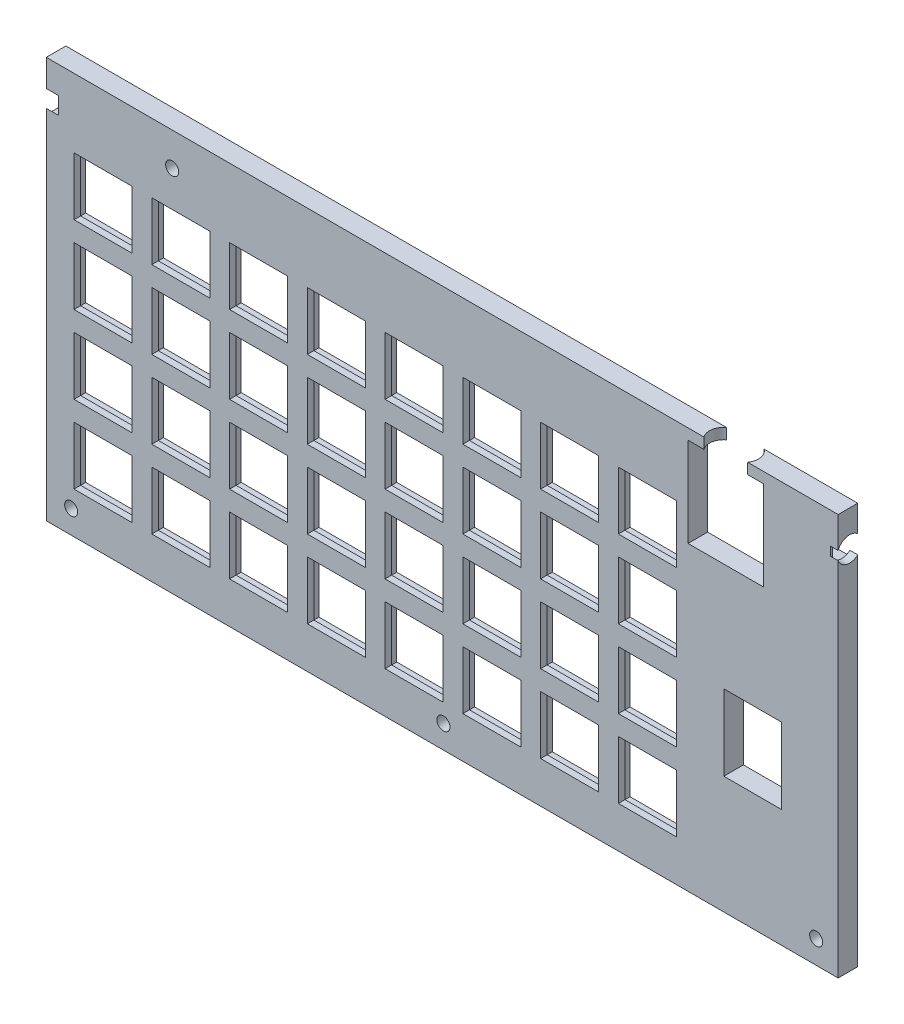
SolidWorks part; units mm, degrees
note: The reader was unsure of these and kept them because the rebuilt part matched: shared geometry of "Sketch1<5>", "Sketch1<6>", "Sketch1<7>", "Sketch4<3>", "Sketch5<3>".
other "Markup1"
sketch "Sketch7" plane through (238.5833, -190.4008, 4.8) normal (0.0408, -0.0399, 0.9984) x (0.9992, -0.0006, -0.0409)
material "Custom Plastic"
ref_plane "Front Plane" through (0, 0, 0) normal (0, 0, 1) x (1, 0, 0)
ref_plane "Top Plane" through (0, 0, 0) normal (0, 1, 0) x (1, 0, 0)
ref_plane "Right Plane" through (0, 0, 0) normal (1, 0, 0) x (0, 0, -1)
sketch "Sketch1" plane through (0, 0, 0) normal (0, 0, 1) x (1, 0, 0)
  line L0 (54.0943, -97.1368) -> (55.0943, -97.1368) construction
  line L1 (51.4043, -123.1268) -> (65.6043, -123.1268)
  line L2 (51.4043, -123.1268) -> (51.4043, -108.9268)
  line L3 (51.4043, -108.9268) -> (65.6043, -108.9268)
  line L4 (65.6043, -123.1268) -> (65.6043, -108.9268)
  line L5 (51.4043, -123.1268) -> (65.6043, -108.9268) construction
  line L6 (51.4043, -108.9268) -> (65.6043, -123.1268) construction
  line L7 (70.4543, -123.1268) -> (70.4543, -108.9268)
  line L8 (70.4543, -123.1268) -> (84.6543, -123.1268)
  line L9 (84.6543, -123.1268) -> (84.6543, -108.9268)
  line L10 (70.4543, -108.9268) -> (84.6543, -108.9268)
  line L11 (89.5043, -123.1268) -> (89.5043, -108.9268)
  line L12 (89.5043, -123.1268) -> (103.7043, -123.1268)
  line L13 (103.7043, -123.1268) -> (103.7043, -108.9268)
  line L14 (89.5043, -108.9268) -> (103.7043, -108.9268)
  line L15 (108.5543, -123.1268) -> (108.5543, -108.9268)
  line L16 (108.5543, -123.1268) -> (122.7543, -123.1268)
  line L17 (122.7543, -123.1268) -> (122.7543, -108.9268)
  line L18 (108.5543, -108.9268) -> (122.7543, -108.9268)
  line L19 (127.6043, -123.1268) -> (127.6043, -108.9268)
  line L20 (127.6043, -123.1268) -> (141.8043, -123.1268)
  line L21 (141.8043, -123.1268) -> (141.8043, -108.9268)
  line L22 (127.6043, -108.9268) -> (141.8043, -108.9268)
  line L23 (146.6543, -123.1268) -> (146.6543, -108.9268)
  line L24 (146.6543, -123.1268) -> (160.8543, -123.1268)
  line L25 (160.8543, -123.1268) -> (160.8543, -108.9268)
  line L26 (146.6543, -108.9268) -> (160.8543, -108.9268)
  line L27 (165.7043, -123.1268) -> (165.7043, -108.9268)
  line L28 (165.7043, -123.1268) -> (179.9043, -123.1268)
  line L29 (179.9043, -123.1268) -> (179.9043, -108.9268)
  line L30 (165.7043, -108.9268) -> (179.9043, -108.9268)
  line L31 (184.7543, -123.1268) -> (184.7543, -108.9268)
  line L32 (184.7543, -123.1268) -> (198.9543, -123.1268)
  line L33 (198.9543, -123.1268) -> (198.9543, -108.9268)
  line L34 (184.7543, -108.9268) -> (198.9543, -108.9268)
  line L35 (70.4543, -142.1768) -> (70.4543, -127.9768)
  line L36 (70.4543, -142.1768) -> (84.6543, -142.1768)
  line L37 (84.6543, -142.1768) -> (84.6543, -127.9768)
  line L38 (70.4543, -127.9768) -> (84.6543, -127.9768)
  line L39 (89.5043, -142.1768) -> (89.5043, -127.9768)
  line L40 (89.5043, -142.1768) -> (103.7043, -142.1768)
  line L41 (103.7043, -142.1768) -> (103.7043, -127.9768)
  line L42 (89.5043, -127.9768) -> (103.7043, -127.9768)
  line L43 (108.5543, -142.1768) -> (108.5543, -127.9768)
  line L44 (108.5543, -142.1768) -> (122.7543, -142.1768)
  line L45 (122.7543, -142.1768) -> (122.7543, -127.9768)
  line L46 (108.5543, -127.9768) -> (122.7543, -127.9768)
  line L47 (127.6043, -142.1768) -> (127.6043, -127.9768)
  line L48 (127.6043, -142.1768) -> (141.8043, -142.1768)
  line L49 (141.8043, -142.1768) -> (141.8043, -127.9768)
  line L50 (127.6043, -127.9768) -> (141.8043, -127.9768)
  line L51 (146.6543, -142.1768) -> (146.6543, -127.9768)
  line L52 (146.6543, -142.1768) -> (160.8543, -142.1768)
  line L53 (160.8543, -142.1768) -> (160.8543, -127.9768)
  line L54 (146.6543, -127.9768) -> (160.8543, -127.9768)
  line L55 (165.7043, -142.1768) -> (165.7043, -127.9768)
  line L56 (165.7043, -142.1768) -> (179.9043, -142.1768)
  line L57 (179.9043, -142.1768) -> (179.9043, -127.9768)
  line L58 (165.7043, -127.9768) -> (179.9043, -127.9768)
  line L59 (184.7543, -142.1768) -> (184.7543, -127.9768)
  line L60 (184.7543, -142.1768) -> (198.9543, -142.1768)
  line L61 (198.9543, -142.1768) -> (198.9543, -127.9768)
  line L62 (184.7543, -127.9768) -> (198.9543, -127.9768)
  line L63 (70.4543, -161.2268) -> (70.4543, -147.0268)
  line L64 (70.4543, -161.2268) -> (84.6543, -161.2268)
  line L65 (84.6543, -161.2268) -> (84.6543, -147.0268)
  line L66 (70.4543, -147.0268) -> (84.6543, -147.0268)
  line L67 (89.5043, -161.2268) -> (89.5043, -147.0268)
  line L68 (89.5043, -161.2268) -> (103.7043, -161.2268)
  line L69 (103.7043, -161.2268) -> (103.7043, -147.0268)
  line L70 (89.5043, -147.0268) -> (103.7043, -147.0268)
  line L71 (108.5543, -161.2268) -> (108.5543, -147.0268)
  line L72 (108.5543, -161.2268) -> (122.7543, -161.2268)
  line L73 (122.7543, -161.2268) -> (122.7543, -147.0268)
  line L74 (108.5543, -147.0268) -> (122.7543, -147.0268)
  line L75 (127.6043, -161.2268) -> (127.6043, -147.0268)
  line L76 (127.6043, -161.2268) -> (141.8043, -161.2268)
  line L77 (141.8043, -161.2268) -> (141.8043, -147.0268)
  line L78 (127.6043, -147.0268) -> (141.8043, -147.0268)
  line L79 (146.6543, -161.2268) -> (146.6543, -147.0268)
  line L80 (146.6543, -161.2268) -> (160.8543, -161.2268)
  line L81 (160.8543, -161.2268) -> (160.8543, -147.0268)
  line L82 (146.6543, -147.0268) -> (160.8543, -147.0268)
  line L83 (165.7043, -161.2268) -> (165.7043, -147.0268)
  line L84 (165.7043, -161.2268) -> (179.9043, -161.2268)
  line L85 (179.9043, -161.2268) -> (179.9043, -147.0268)
  line L86 (165.7043, -147.0268) -> (179.9043, -147.0268)
  line L87 (184.7543, -161.2268) -> (184.7543, -147.0268)
  line L88 (184.7543, -161.2268) -> (198.9543, -161.2268)
  line L89 (198.9543, -161.2268) -> (198.9543, -147.0268)
  line L90 (184.7543, -147.0268) -> (198.9543, -147.0268)
  line L91 (70.4543, -180.2768) -> (70.4543, -166.0768)
  line L92 (70.4543, -180.2768) -> (84.6543, -180.2768)
  line L93 (84.6543, -180.2768) -> (84.6543, -166.0768)
  line L94 (70.4543, -166.0768) -> (84.6543, -166.0768)
  line L95 (89.5043, -180.2768) -> (89.5043, -166.0768)
  line L96 (89.5043, -180.2768) -> (103.7043, -180.2768)
  line L97 (103.7043, -180.2768) -> (103.7043, -166.0768)
  line L98 (89.5043, -166.0768) -> (103.7043, -166.0768)
  line L99 (108.5543, -180.2768) -> (108.5543, -166.0768)
  line L100 (108.5543, -180.2768) -> (122.7543, -180.2768)
  line L101 (122.7543, -180.2768) -> (122.7543, -166.0768)
  line L102 (108.5543, -166.0768) -> (122.7543, -166.0768)
  line L103 (127.6043, -180.2768) -> (127.6043, -166.0768)
  line L104 (127.6043, -180.2768) -> (141.8043, -180.2768)
  line L105 (141.8043, -180.2768) -> (141.8043, -166.0768)
  line L106 (127.6043, -166.0768) -> (141.8043, -166.0768)
  line L107 (146.6543, -180.2768) -> (146.6543, -166.0768)
  line L108 (146.6543, -180.2768) -> (160.8543, -180.2768)
  line L109 (160.8543, -180.2768) -> (160.8543, -166.0768)
  line L110 (146.6543, -166.0768) -> (160.8543, -166.0768)
  line L111 (165.7043, -180.2768) -> (165.7043, -166.0768)
  line L112 (165.7043, -180.2768) -> (179.9043, -180.2768)
  line L113 (179.9043, -180.2768) -> (179.9043, -166.0768)
  line L114 (165.7043, -166.0768) -> (179.9043, -166.0768)
  line L115 (184.7543, -180.2768) -> (184.7543, -166.0768)
  line L116 (184.7543, -180.2768) -> (198.9543, -180.2768)
  line L117 (198.9543, -180.2768) -> (198.9543, -166.0768)
  line L118 (184.7543, -166.0768) -> (198.9543, -166.0768)
  line L119 (51.4043, -142.1768) -> (51.4043, -127.9768)
  line L120 (51.4043, -142.1768) -> (65.6043, -142.1768)
  line L121 (65.6043, -142.1768) -> (65.6043, -127.9768)
  line L122 (51.4043, -127.9768) -> (65.6043, -127.9768)
  line L123 (51.4043, -161.2268) -> (51.4043, -147.0268)
  line L124 (51.4043, -161.2268) -> (65.6043, -161.2268)
  line L125 (65.6043, -161.2268) -> (65.6043, -147.0268)
  line L126 (51.4043, -147.0268) -> (65.6043, -147.0268)
  line L127 (51.4043, -180.2768) -> (51.4043, -166.0768)
  line L128 (51.4043, -180.2768) -> (65.6043, -180.2768)
  line L129 (65.6043, -180.2768) -> (65.6043, -166.0768)
  line L130 (51.4043, -166.0768) -> (65.6043, -166.0768)
  line L131 (238.5833, -190.4008) -> (238.5833, -173.7718) construction
  line L132 (44.6073, -92.0718) -> (238.5833, -92.0718)
  line L133 (44.6073, -92.0718) -> (44.6073, -190.4008)
  line L134 (44.6073, -190.4008) -> (238.5833, -190.4008)
  line L135 (238.5833, -92.0718) -> (238.5833, -190.4008)
  line L136 (44.6073, -190.4008) -> (44.6073, -103.6591) construction
  line L137 (238.5833, -190.4008) -> (44.6073, -190.4008) construction
  line L138 (149.2419, -92.0718) -> (44.6073, -92.0718) construction
  line L140 (130.7973, -100.9138) -> (130.7973, -98.8818) construction
  line L141 (53.3943, -97.3368) -> (53.3943, -96.9368)
  line L142 (53.3943, -96.9368) -> (55.7943, -96.9368)
  line L143 (55.7943, -96.9368) -> (55.7943, -97.3368)
  line L144 (55.7943, -97.3368) -> (59.7643, -97.3368)
  line L145 (59.7643, -97.3368) -> (59.7643, -104.2368)
  line L146 (59.7643, -104.2368) -> (56.7943, -104.2368)
  line L147 (56.7943, -104.2368) -> (56.7943, -104.6368)
  line L148 (56.7943, -104.6368) -> (54.3943, -104.6368)
  line L149 (54.3943, -104.6368) -> (54.3943, -104.2368)
  line L150 (54.3943, -104.2368) -> (44.6073, -104.2368)
  line L151 (44.6073, -104.2368) -> (44.6073, -97.3368)
  line L152 (44.6073, -97.3368) -> (53.3943, -97.3368)
  line L153 (49.9143, -97.5368) -> (50.7143, -97.5368) construction
  line L154 (56.4643, -97.5368) -> (57.2643, -97.5368) construction
  line L155 (50.7043, -104.0368) -> (49.9043, -104.0368) construction
  line L156 (56.0943, -104.4368) -> (55.0943, -104.4368) construction
  line L157 (58.4643, -104.0368) -> (57.6643, -104.0368) construction
  line L158 (59.5643, -103.9368) -> (59.5643, -97.6368) construction
  line L159 (238.5833, -104.2368) -> (230.8283, -104.2368)
  line L160 (230.8283, -104.2368) -> (230.8283, -104.6368)
  line L161 (230.8283, -104.6368) -> (228.4283, -104.6368)
  line L162 (228.4283, -104.6368) -> (228.4283, -104.2368)
  line L163 (228.4283, -104.2368) -> (224.4583, -104.2368)
  line L164 (224.4583, -104.2368) -> (224.4583, -97.3368)
  line L165 (224.4583, -97.3368) -> (227.4283, -97.3368)
  line L166 (227.4283, -97.3368) -> (227.4283, -96.9368)
  line L167 (227.4283, -96.9368) -> (229.8283, -96.9368)
  line L168 (229.8283, -96.9368) -> (229.8283, -97.3368)
  line L169 (229.8283, -97.3368) -> (238.5833, -97.3368)
  line L170 (238.5833, -97.3368) -> (238.5833, -104.2368)
  line L171 (229.1283, -97.1368) -> (228.1283, -97.1368) construction
  line L172 (227.7583, -104.0368) -> (226.9583, -104.0368) construction
  line L173 (234.3083, -104.0368) -> (233.5083, -104.0368) construction
  line L174 (230.1283, -104.4368) -> (229.1283, -104.4368) construction
  line L175 (224.6583, -97.6368) -> (224.6583, -103.9368) construction
  line L176 (225.7583, -97.5368) -> (226.5583, -97.5368) construction
  line L177 (233.5183, -97.5368) -> (234.3183, -97.5368) construction
  line L178 (130.7973, -98.6278) -> (143.4973, -98.6278)
  line L179 (130.7973, -98.6278) -> (130.7973, -101.1678)
  line L180 (130.7973, -101.1678) -> (143.4973, -101.1678)
  line L181 (143.4973, -98.6278) -> (143.4973, -101.1678)
  line L182 (143.4973, -98.8818) -> (143.4973, -100.9138) construction
  line L183 (136.1313, -98.6278) -> (138.1633, -98.6278) construction
  line L184 (140.7033, -101.1678) -> (138.6713, -101.1678) construction
  line L185 (202.3109, -103.4561) -> (202.3109, -104.0561) construction
  line L186 (201.8109, -92.0718) -> (220.3109, -92.0718)
  line L187 (201.8109, -92.0718) -> (201.8109, -116.5961)
  line L188 (201.8109, -116.5961) -> (220.3109, -116.5961)
  line L189 (220.3109, -92.0718) -> (220.3109, -116.5961)
  line L190 (219.8109, -108.5361) -> (219.8109, -109.1361) construction
  line L191 (204.1909, -116.0961) -> (217.9309, -116.0961) construction
  line L192 (222.3783, -107.3018) -> (221.5783, -107.3018) construction
  line L193 (221.3783, -105.5018) -> (222.5783, -105.5018)
  line L194 (221.3783, -105.5018) -> (221.3783, -107.5018)
  line L195 (221.3783, -107.5018) -> (222.5783, -107.5018)
  line L196 (222.5783, -105.5018) -> (222.5783, -107.5018)
  line L197 (222.3783, -107.0018) -> (222.3783, -106.0018) construction
  line L198 (221.5783, -107.0018) -> (221.5783, -106.0018) construction
  line L199 (222.3783, -105.7018) -> (221.5783, -105.7018) construction
  line L200 (62.0853, -100.1588) -> (62.0853, -101.6688) construction
  line L201 (62.4853, -100.1588) -> (61.6853, -100.1588) construction
  line L202 (62.4853, -101.6688) -> (61.6853, -101.6688) construction
  line L203 (62.4853, -100.1138) -> (61.6853, -100.1138) construction
  line L204 (61.4853, -101.9138) -> (62.6853, -101.9138)
  line L205 (61.4853, -101.9138) -> (61.4853, -99.9138)
  line L206 (61.4853, -99.9138) -> (62.6853, -99.9138)
  line L207 (62.6853, -101.9138) -> (62.6853, -99.9138)
  line L208 (61.4853, -101.9138) -> (62.6853, -99.9138) construction
  line L209 (61.4853, -99.9138) -> (62.6853, -101.9138) construction
  line L210 (62.4853, -101.4138) -> (62.4853, -100.4138) construction
  line L211 (217.9243, -158.5918) -> (219.9563, -158.5918) construction
  line L212 (210.5803, -143.0518) -> (224.7503, -143.0518)
  line L213 (210.5803, -143.0518) -> (210.5803, -161.5918)
  line L214 (210.5803, -161.5918) -> (224.7503, -161.5918)
  line L215 (224.7503, -143.0518) -> (224.7503, -161.5918)
  line L216 (217.4113, -146.0518) -> (215.3793, -146.0518) construction
  line L217 (222.7503, -153.3378) -> (222.7503, -151.3058) construction
  line L218 (68.5043, -125.0768) -> (68.5043, -106.9768)
  line L219 (49.4543, -125.0768) -> (67.5543, -125.0768)
  line L220 (49.4543, -125.0768) -> (49.4543, -106.9768)
  line L221 (49.4543, -106.9768) -> (67.5543, -106.9768)
  line L222 (67.5543, -125.0768) -> (67.5543, -106.9768)
  line L223 (49.4543, -125.0768) -> (67.5543, -106.9768) construction
  line L224 (49.4543, -106.9768) -> (67.5543, -125.0768) construction
  line L225 (68.5043, -125.0768) -> (86.6043, -125.0768)
  line L226 (86.6043, -125.0768) -> (86.6043, -106.9768)
  line L227 (68.5043, -106.9768) -> (86.6043, -106.9768)
  line L228 (87.5543, -125.0768) -> (87.5543, -106.9768)
  line L229 (87.5543, -125.0768) -> (105.6543, -125.0768)
  line L230 (105.6543, -125.0768) -> (105.6543, -106.9768)
  line L231 (87.5543, -106.9768) -> (105.6543, -106.9768)
  line L232 (106.6043, -125.0768) -> (106.6043, -106.9768)
  line L233 (106.6043, -125.0768) -> (124.7043, -125.0768)
  line L234 (124.7043, -125.0768) -> (124.7043, -106.9768)
  line L235 (106.6043, -106.9768) -> (124.7043, -106.9768)
  line L236 (125.6543, -125.0768) -> (125.6543, -106.9768)
  line L237 (125.6543, -125.0768) -> (143.7543, -125.0768)
  line L238 (143.7543, -125.0768) -> (143.7543, -106.9768)
  line L239 (125.6543, -106.9768) -> (143.7543, -106.9768)
  line L240 (144.7043, -125.0768) -> (144.7043, -106.9768)
  line L241 (144.7043, -125.0768) -> (162.8043, -125.0768)
  line L242 (162.8043, -125.0768) -> (162.8043, -106.9768)
  line L243 (144.7043, -106.9768) -> (162.8043, -106.9768)
  line L244 (163.7543, -125.0768) -> (163.7543, -106.9768)
  line L245 (163.7543, -125.0768) -> (181.8543, -125.0768)
  line L246 (181.8543, -125.0768) -> (181.8543, -106.9768)
  line L247 (163.7543, -106.9768) -> (181.8543, -106.9768)
  line L248 (182.8043, -125.0768) -> (182.8043, -106.9768)
  line L249 (182.8043, -125.0768) -> (200.9043, -125.0768)
  line L250 (200.9043, -125.0768) -> (200.9043, -106.9768)
  line L251 (182.8043, -106.9768) -> (200.9043, -106.9768)
  line L252 (68.5043, -144.1268) -> (68.5043, -126.0268)
  line L253 (68.5043, -144.1268) -> (86.6043, -144.1268)
  line L254 (86.6043, -144.1268) -> (86.6043, -126.0268)
  line L255 (68.5043, -126.0268) -> (86.6043, -126.0268)
  line L256 (87.5543, -144.1268) -> (87.5543, -126.0268)
  line L257 (87.5543, -144.1268) -> (105.6543, -144.1268)
  line L258 (105.6543, -144.1268) -> (105.6543, -126.0268)
  line L259 (87.5543, -126.0268) -> (105.6543, -126.0268)
  line L260 (106.6043, -144.1268) -> (106.6043, -126.0268)
  line L261 (106.6043, -144.1268) -> (124.7043, -144.1268)
  line L262 (124.7043, -144.1268) -> (124.7043, -126.0268)
  line L263 (106.6043, -126.0268) -> (124.7043, -126.0268)
  line L264 (125.6543, -144.1268) -> (125.6543, -126.0268)
  line L265 (125.6543, -144.1268) -> (143.7543, -144.1268)
  line L266 (143.7543, -144.1268) -> (143.7543, -126.0268)
  line L267 (125.6543, -126.0268) -> (143.7543, -126.0268)
  line L268 (144.7043, -144.1268) -> (144.7043, -126.0268)
  line L269 (144.7043, -144.1268) -> (162.8043, -144.1268)
  line L270 (162.8043, -144.1268) -> (162.8043, -126.0268)
  line L271 (144.7043, -126.0268) -> (162.8043, -126.0268)
  line L272 (163.7543, -144.1268) -> (163.7543, -126.0268)
  line L273 (163.7543, -144.1268) -> (181.8543, -144.1268)
  line L274 (181.8543, -144.1268) -> (181.8543, -126.0268)
  line L275 (163.7543, -126.0268) -> (181.8543, -126.0268)
  line L276 (182.8043, -144.1268) -> (182.8043, -126.0268)
  line L277 (182.8043, -144.1268) -> (200.9043, -144.1268)
  line L278 (200.9043, -144.1268) -> (200.9043, -126.0268)
  line L279 (182.8043, -126.0268) -> (200.9043, -126.0268)
  line L280 (68.5043, -163.1768) -> (68.5043, -145.0768)
  line L281 (68.5043, -163.1768) -> (86.6043, -163.1768)
  line L282 (86.6043, -163.1768) -> (86.6043, -145.0768)
  line L283 (68.5043, -145.0768) -> (86.6043, -145.0768)
  line L284 (87.5543, -163.1768) -> (87.5543, -145.0768)
  line L285 (87.5543, -163.1768) -> (105.6543, -163.1768)
  line L286 (105.6543, -163.1768) -> (105.6543, -145.0768)
  line L287 (87.5543, -145.0768) -> (105.6543, -145.0768)
  line L288 (106.6043, -163.1768) -> (106.6043, -145.0768)
  line L289 (106.6043, -163.1768) -> (124.7043, -163.1768)
  line L290 (124.7043, -163.1768) -> (124.7043, -145.0768)
  line L291 (106.6043, -145.0768) -> (124.7043, -145.0768)
  line L292 (125.6543, -163.1768) -> (125.6543, -145.0768)
  line L293 (125.6543, -163.1768) -> (143.7543, -163.1768)
  line L294 (143.7543, -163.1768) -> (143.7543, -145.0768)
  line L295 (125.6543, -145.0768) -> (143.7543, -145.0768)
  line L296 (144.7043, -163.1768) -> (144.7043, -145.0768)
  line L297 (144.7043, -163.1768) -> (162.8043, -163.1768)
  line L298 (162.8043, -163.1768) -> (162.8043, -145.0768)
  line L299 (144.7043, -145.0768) -> (162.8043, -145.0768)
  line L300 (163.7543, -163.1768) -> (163.7543, -145.0768)
  line L301 (163.7543, -163.1768) -> (181.8543, -163.1768)
  line L302 (181.8543, -163.1768) -> (181.8543, -145.0768)
  line L303 (163.7543, -145.0768) -> (181.8543, -145.0768)
  line L304 (182.8043, -163.1768) -> (182.8043, -145.0768)
  line L305 (182.8043, -163.1768) -> (200.9043, -163.1768)
  line L306 (200.9043, -163.1768) -> (200.9043, -145.0768)
  line L307 (182.8043, -145.0768) -> (200.9043, -145.0768)
  line L308 (68.5043, -182.2268) -> (68.5043, -164.1268)
  line L309 (68.5043, -182.2268) -> (86.6043, -182.2268)
  line L310 (86.6043, -182.2268) -> (86.6043, -164.1268)
  line L311 (68.5043, -164.1268) -> (86.6043, -164.1268)
  line L312 (87.5543, -182.2268) -> (87.5543, -164.1268)
  line L313 (87.5543, -182.2268) -> (105.6543, -182.2268)
  line L314 (105.6543, -182.2268) -> (105.6543, -164.1268)
  line L315 (87.5543, -164.1268) -> (105.6543, -164.1268)
  line L316 (106.6043, -182.2268) -> (106.6043, -164.1268)
  line L317 (106.6043, -182.2268) -> (124.7043, -182.2268)
  line L318 (124.7043, -182.2268) -> (124.7043, -164.1268)
  line L319 (106.6043, -164.1268) -> (124.7043, -164.1268)
  line L320 (125.6543, -182.2268) -> (125.6543, -164.1268)
  line L321 (125.6543, -182.2268) -> (143.7543, -182.2268)
  line L322 (143.7543, -182.2268) -> (143.7543, -164.1268)
  line L323 (125.6543, -164.1268) -> (143.7543, -164.1268)
  line L324 (144.7043, -182.2268) -> (144.7043, -164.1268)
  line L325 (144.7043, -182.2268) -> (162.8043, -182.2268)
  line L326 (162.8043, -182.2268) -> (162.8043, -164.1268)
  line L327 (144.7043, -164.1268) -> (162.8043, -164.1268)
  line L328 (163.7543, -182.2268) -> (163.7543, -164.1268)
  line L329 (163.7543, -182.2268) -> (181.8543, -182.2268)
  line L330 (181.8543, -182.2268) -> (181.8543, -164.1268)
  line L331 (163.7543, -164.1268) -> (181.8543, -164.1268)
  line L332 (182.8043, -182.2268) -> (182.8043, -164.1268)
  line L333 (182.8043, -182.2268) -> (200.9043, -182.2268)
  line L334 (200.9043, -182.2268) -> (200.9043, -164.1268)
  line L335 (182.8043, -164.1268) -> (200.9043, -164.1268)
  line L336 (49.4543, -144.1268) -> (49.4543, -126.0268)
  line L337 (49.4543, -144.1268) -> (67.5543, -144.1268)
  line L338 (67.5543, -144.1268) -> (67.5543, -126.0268)
  line L339 (49.4543, -126.0268) -> (67.5543, -126.0268)
  line L340 (49.4543, -163.1768) -> (49.4543, -145.0768)
  line L341 (49.4543, -163.1768) -> (67.5543, -163.1768)
  line L342 (67.5543, -163.1768) -> (67.5543, -145.0768)
  line L343 (49.4543, -145.0768) -> (67.5543, -145.0768)
  line L344 (49.4543, -182.2268) -> (49.4543, -164.1268)
  line L345 (49.4543, -182.2268) -> (67.5543, -182.2268)
  line L346 (67.5543, -182.2268) -> (67.5543, -164.1268)
  line L347 (49.4543, -164.1268) -> (67.5543, -164.1268)
  circle A0 centre (75.4383, -100.2028) radius 1.6
  circle A1 centre (75.4383, -100.2028) radius 1.6 construction
  circle A2 centre (50.7063, -184.7338) radius 1.6
  circle A3 centre (50.7063, -184.7338) radius 1.6 construction
  circle A4 centre (141.8923, -184.7338) radius 1.6
  circle A5 centre (141.8923, -184.7338) radius 1.6 construction
  circle A6 centre (233.2053, -184.7338) radius 1.6
  circle A7 centre (233.2053, -184.7338) radius 1.6 construction
  point P0 (58.5043, -116.0268)
  point P146 (54.5943, -97.1368)
  point P166 (50.3043, -104.0368)
  point P252 (221.9783, -107.3018)
  point P253 (221.9783, -107.5018)
  point P256 (222.3783, -106.5018)
  point P257 (222.5783, -106.5018)
  point P268 (62.0853, -100.9138)
  point P281 (217.6653, -143.0518)
  point P295 (58.5043, -116.0268)
  dimension "D1" = 14.2
  dimension "D2" = 14.2
  dimension "D5" = 0.2
  dimension "D6" = 0.2
  dimension "D7" = 0.2
  dimension "D8" = 0.2
  dimension "D9" = 0.2
  dimension "D10" = 0.2
  dimension "D11" = 0.2
  dimension "D12" = 0.2
  dimension "D13" = 0.2
  dimension "D14" = 0.2
  dimension "D15" = 0.2
  dimension "D16" = 0.2
  dimension "D17" = 0.2
  dimension "D18" = 0.2
  dimension "D19" = 0.2
  dimension "D20" = 0.2
  dimension "D21" = 0.2
  dimension "D22" = 0.2
  dimension "D23" = 0.2
  dimension "D24" = 0.2
  dimension "D25" = 0.2
  dimension "D26" = 0.2
  dimension "D27" = 19.05
  dimension "D28" = 19.05
  dimension "D29" = 0.5
  dimension "D30" = 0.5
  dimension "D31" = 0.5
  dimension "D32" = 0.2
  dimension "D33" = 0.2
  dimension "D34" = 0.2
  dimension "D35" = 0.2
  dimension "D36" = 3
  dimension "D37" = 3
  dimension "D38" = 2
  dimension "D41" = 18.1
  dimension "D42" = 18.1
  dimension "D45" = 19.05
  dimension "D46" = 19.05
  dimension "D3" = 8
  dimension "D4" = 4
  dimension "D43" = 8
  dimension "D44" = 4
extrude "Boss-Extrude1" add sketch "Sketch1" along normal blind 3.2
extrude "Boss-Extrude2" add sketch "Sketch1<5>" along normal blind 1.6 from surface at 3.2
sketch "Sketch1<5>" plane through (0, 0, 0) normal (0, 0, 1) x (1, 0, 0) same geometry as "Sketch1"
extrude "Boss-Extrude3" add sketch "Sketch1<6>" against normal offset from surface (3.65 mm away) 0.7 from surface at 4.8 contours L196 L193 L194 L195 | L204 L207 L206 L205 | L181 L178 L179 L180 starting at face at (221.9783, -106.5018, 4.8)
sketch "Sketch1<6>" plane through (0, 0, 0) normal (0, 0, 1) x (1, 0, 0) same geometry as "Sketch1"
extrude "Boss-Extrude4" add sketch "Sketch1<7>" against normal offset from surface (0.6 mm away) 0.2 from surface at 4.8 contours L169 L168 L167 L166 L165 L164 L163 L162 L161 L160 L159 L135 | L152 L133 L150 L149 L148 L147 L146 L145 L144 L143 L142 L141 starting at face at (143.4923, -184.7338, 4.8)
sketch "Sketch1<7>" plane through (0, 0, 0) normal (0, 0, 1) x (1, 0, 0) same geometry as "Sketch1"
sketch "Sketch4" plane through (238.5833, 0, 0) normal (1, 0, 0) x (0, 0, -1)
  line L1 (-4.2, -97.3368) -> (0, -97.3368)
  line L2 (-4.2, -97.3368) -> (-4.2, -104.2368)
  line L3 (-4.2, -104.2368) -> (0, -104.2368)
  line L4 (0, -97.3368) -> (0, -104.2368)
  circle A0 centre (-2, -100.7868) radius 3
  line M3 (-4.8, -92.0718) -> (-4.8, -190.4008)
  line M6 (0, -104.2368) -> (-4.2, -104.2368)
  line M7 (-4.2, -104.2368) -> (-4.2, -97.3368)
  line M8 (-4.2, -97.3368) -> (0, -97.3368)
  dimension "D1" = 6
extrude "Cut-Extrude1" cut sketch "Sketch4" against normal up to surface (1.925 mm away) contours L2 A0 M3 | L2 A0 L4 | L4 A0
sketch "Sketch5" plane through (44.6073, 0, 0) normal (-1, 0, 0) x (0, 0, 1)
  line L1 (0, -97.3368) -> (4.2, -97.3368)
  line L2 (0, -97.3368) -> (0, -104.2368)
  line L3 (0, -104.2368) -> (4.2, -104.2368)
  line L4 (4.2, -97.3368) -> (4.2, -104.2368)
  circle A0 centre (2, -100.7868) radius 3.5
  arc A1 (0, -97.9145) -> (0, -103.6591) centre (2, -100.7868) ccw construction
  line M3 (4.8, -190.4008) -> (4.8, -92.0718)
  line M6 (0, -97.3368) -> (4.2, -97.3368)
  line M7 (4.2, -97.3368) -> (4.2, -104.2368)
  line M8 (4.2, -104.2368) -> (0, -104.2368)
extrude "Cut-Extrude2" cut sketch "Sketch5" against normal up to surface (2.957 mm away) contours L2 A0 | L4 A0 L2 | L4 A0 M3
sketch "Sketch6" plane through (0, -92.0718, 0) normal (0, 1, 0) x (1, 0, 0)
  line L0 (207.8409, -3.155) -> (207.8409, -2.445) construction
  line L1 (214.2809, -2.445) -> (214.2809, -3.155) construction
  line L2 (214.2809, -2.8) -> (207.8409, -2.8) construction
  line L3 (208.5609, -2.8) -> (213.5609, -2.8) construction
  line L4 (208.5609, 0.7) -> (213.5609, 0.7)
  line L5 (208.5609, -6.3) -> (213.5609, -6.3)
  line L7 (201.8109, -4.8) -> (220.3109, -4.8)
  line L8 (201.8109, -4.8) -> (201.8109, 0)
  line L9 (201.8109, 0) -> (220.3109, 0)
  line L10 (220.3109, -4.8) -> (220.3109, 0)
  arc A0 (208.5609, 0.7) -> (208.5609, -6.3) centre (208.5609, -2.8) ccw
  arc A1 (213.5609, -6.3) -> (213.5609, 0.7) centre (213.5609, -2.8) ccw
  point P12 (211.0609, -2.8)
  point P17 (205.0609, -2.8)
  point P18 (217.0609, -2.8)
  line M4 (220.3109, 0) -> (220.3109, -4.8)
  dimension "D1" = 7
  dimension "D2" = 12
extrude "Boss-Extrude5" add sketch "Sketch6" against normal offset from surface (2.6243 mm away) 0.4 contours A0 L9 L8 L7 | A1 L7 L9 M4
extrude "Boss-Extrude6" add sketch "Sketch4<3>" against normal up to surface (1.925 mm away) contours A0 L4 M8 M7 | A0 L4 M7 M6 up to face at (236.6583, -100.7868, 4.523)
sketch "Sketch4<3>" plane through (238.5833, 0, 0) normal (1, 0, 0) x (0, 0, -1) same geometry as "Sketch4"
extrude "Boss-Extrude7" add sketch "Sketch5<3>" against normal up to surface (2.957 mm away) contours A0 L2 M7 M6 | A0 L2 M8 M7
sketch "Sketch5<3>" plane through (44.6073, 0, 0) normal (-1, 0, 0) x (0, 0, 1) same geometry as "Sketch5"
